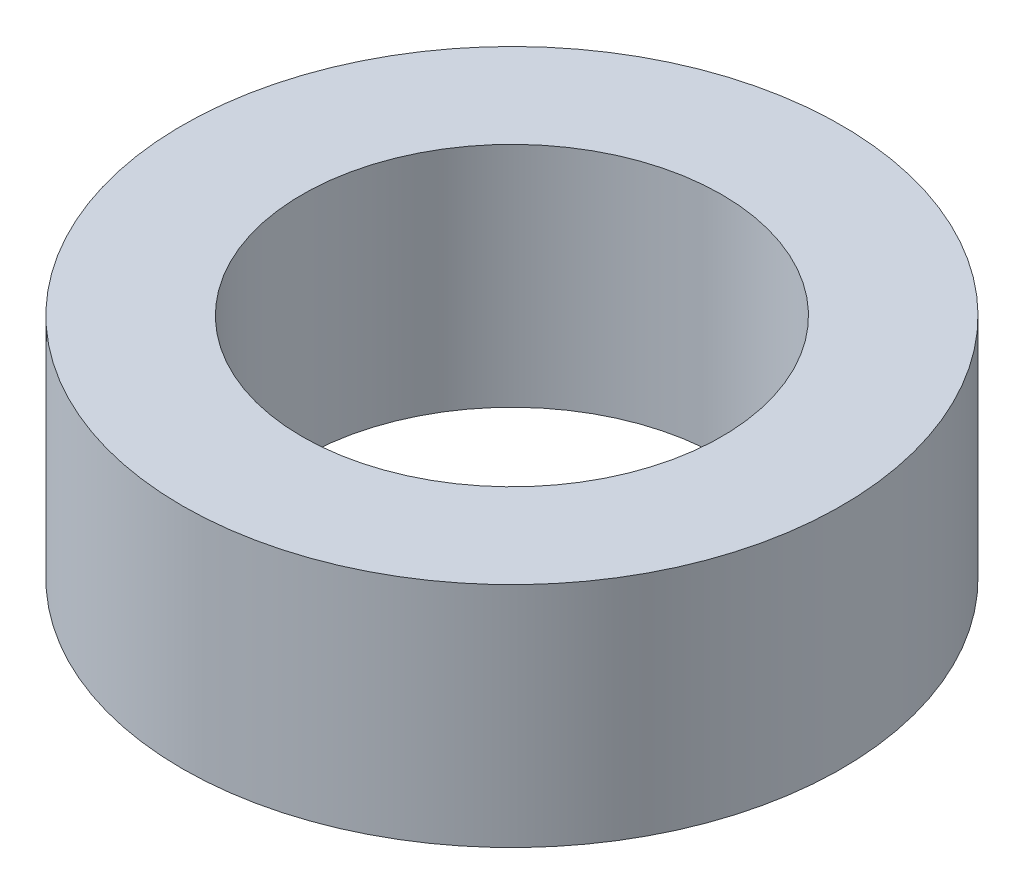
SolidWorks part; units mm, degrees
ref_plane "Front Plane" through (0, 0, 0) normal (0, 0, 1) x (1, 0, 0)
ref_plane "Top Plane" through (0, 0, 0) normal (0, 1, 0) x (1, 0, 0)
ref_plane "Right Plane" through (0, 0, 0) normal (1, 0, 0) x (0, 0, -1)
sketch "Sketch1" plane through (0, 0, 0) normal (0, 1, 0) x (1, 0, 0)
  circle A0 centre (0, 0) radius 27.5
  dimension "FLANGE_OD" = 55
extrude "Boss-Extrude1" add sketch "Sketch1" along normal blind 19
sketch "Sketch2" plane through (0, 0, 0) normal (0, 1, 0) x (1, 0, 0)
  circle A0 centre (0, 0) radius 17.5
  dimension "BORE_D" = 35
extrude "Cut-Extrude1" cut sketch "Sketch2" along normal through all
sketch "Sketch3" plane through (0, 19, 0) normal (0, 1, 0) x (1, 0, 0)
  circle A0 centre (0, 0) radius 10.7946 construction
  circle A1 centre (-10.7946, 0) radius 1.7038
  dimension "BOLT_D" = 3.4075
  dimension "BOLT_PCD" = 21.5891
extrude "Cut-Extrude2" cut sketch "Sketch3" against normal blind 14.1095 rebuild error yes
pattern_circular "CirPattern1" count 5 over 360 rebuild error yes
